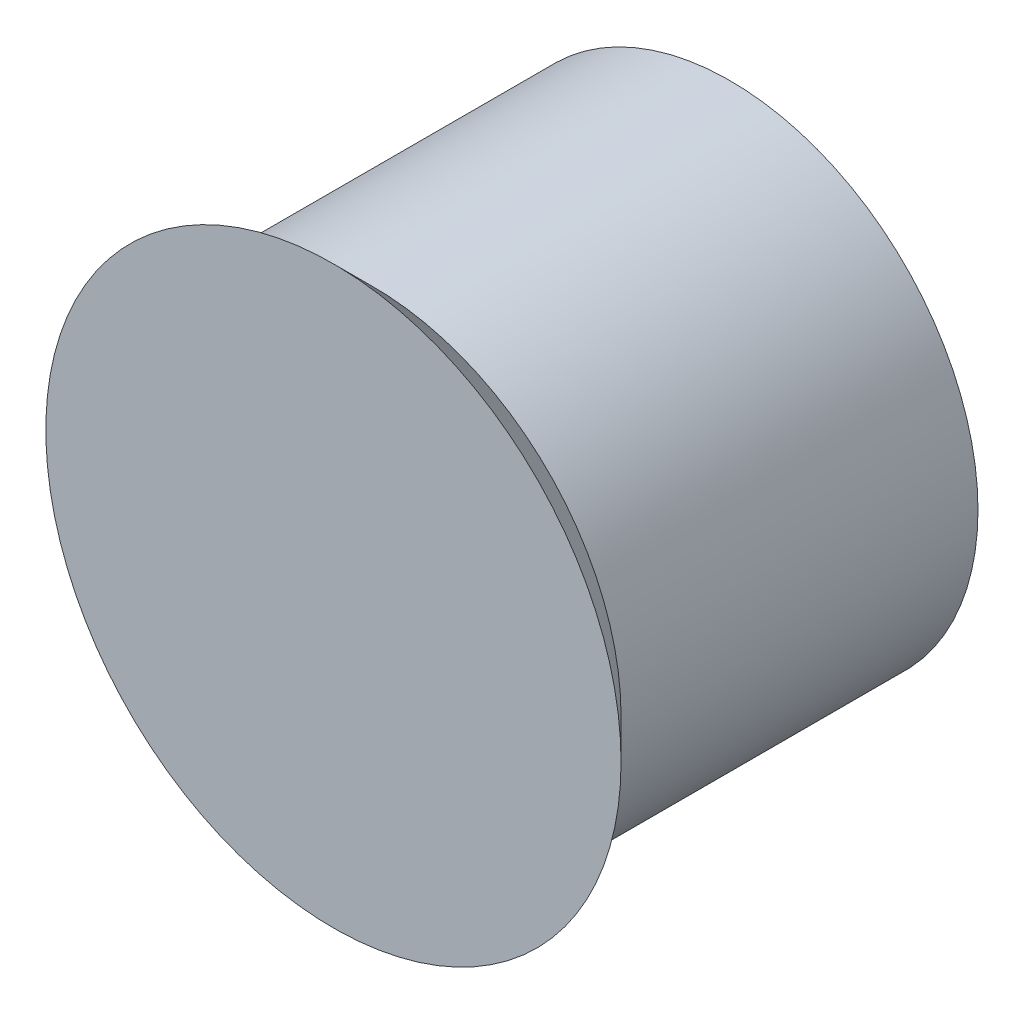
SolidWorks part; units mm, degrees
ref_plane "Ön Düzlem" through (0, 0, 0) normal (0, 0, 1) x (1, 0, 0)
ref_plane "Üst Düzlem" through (0, 0, 0) normal (0, 1, 0) x (1, 0, 0)
ref_plane "Sağ Düzlem" through (0, 0, 0) normal (1, 0, 0) x (0, 0, -1)
sketch "Çizim1" plane through (0, 0, 0) normal (0, 0, 1) x (1, 0, 0)
  circle A0 centre (0, 0) radius 1.25
  dimension "D1" = 2.5
extrude "Yükseklik-Ekstrüzyon1" add sketch "Çizim1" along normal blind 1.8
sketch "Çizim2" plane through (0, 0, 1.8) normal (0, 0, 1) x (1, 0, 0)
  circle A0 centre (0, 0) radius 1.2502
extrude "Yükseklik-Ekstrüzyon2" add sketch "Çizim2" along normal blind 0.2 draft 45 draft outward yes
